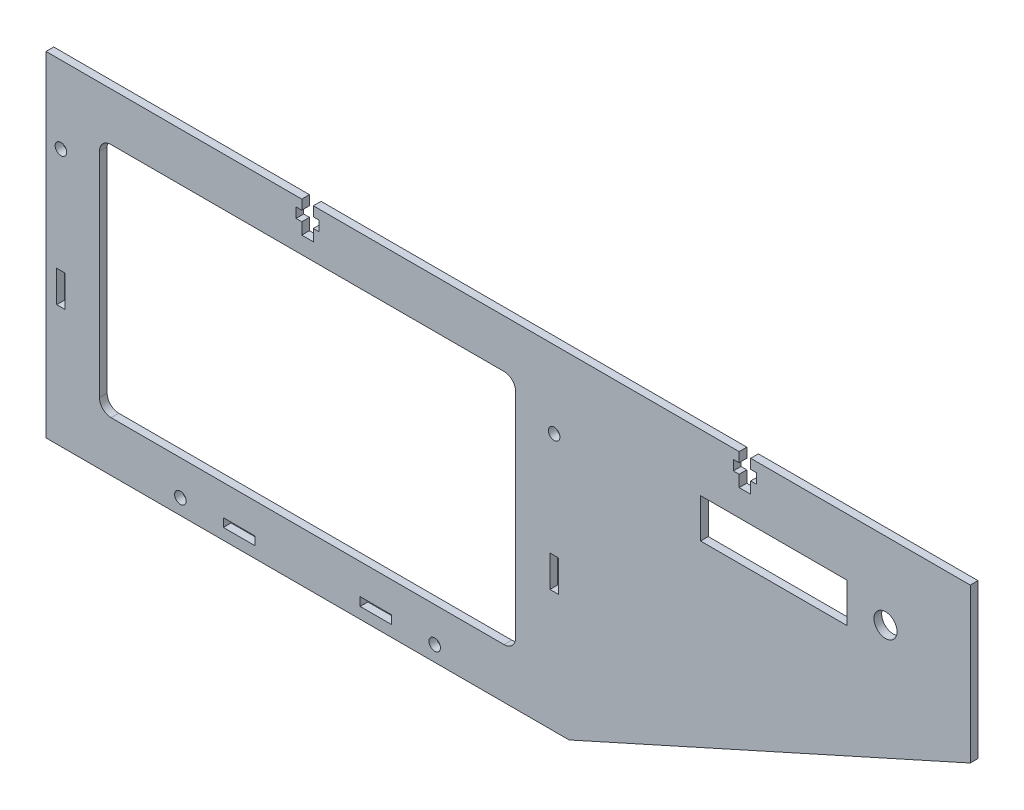
SolidWorks part; units mm, degrees
ref_plane "前视基准面" through (0, 0, 0) normal (0, 0, 1) x (1, 0, 0)
ref_plane "上视基准面" through (0, 0, 0) normal (0, 1, 0) x (1, 0, 0)
ref_plane "右视基准面" through (0, 0, 0) normal (1, 0, 0) x (0, 0, -1)
sketch "草图1" plane through (0, 0, 0) normal (0, 0, 1) x (1, 0, 0)
  line L0 (21.5651, -10.096) -> (13.5651, -8.096) construction
  line L1 (32.8151, -9.096) -> (-33.1849, -9.096) construction
  line L3 (-34.6849, -10.096) -> (-31.6849, -8.096) construction
  line L4 (-21.9349, -10.096) -> (-13.9349, -8.096) construction
  line L5 (-22.0349, -10.196) -> (-13.8349, -10.196)
  line L6 (-13.8349, -7.996) -> (-13.8349, -10.196)
  line L7 (-22.0349, -7.996) -> (-13.8349, -7.996)
  line L8 (-22.0349, -7.996) -> (-22.0349, -10.196)
  line L12 (-52.1849, -13.096) -> (-18.9349, -13.096)
  line L13 (64.9151, 18.2415) -> (62.7151, 18.2415)
  line L15 (34.3151, -10.096) -> (31.3151, -8.096) construction
  line L16 (21.6651, -7.996) -> (21.6651, -10.196)
  line L17 (21.6651, -7.996) -> (13.4651, -7.996)
  line L18 (13.4651, -7.996) -> (13.4651, -10.196)
  line L19 (67.6951, -13.096) -> (18.5651, -13.096)
  line L20 (64.9151, 18.2415) -> (64.9151, 26.4415)
  line L21 (-18.9349, -13.096) -> (18.5651, -13.096)
  line L22 (64.9151, 26.4415) -> (62.7151, 26.4415)
  line L25 (-63.0849, 18.2415) -> (-63.0849, 26.4415)
  line L26 (-65.2849, 26.4415) -> (-63.0849, 26.4415)
  line L27 (-65.2849, 18.2415) -> (-65.2849, 26.4415)
  line L28 (-65.2849, 18.2415) -> (-63.0849, 18.2415)
  line L29 (21.6651, -10.196) -> (13.4651, -10.196)
  line L34 (62.7151, 18.2415) -> (62.7151, 26.4415)
  line L35 (-52.1849, -13.096) -> (-68.0618, -13.096)
  line L41 (-49.1849, 53.779) -> (-49.1849, 33.779) construction
  line L42 (-49.1849, 53.779) -> (-49.1849, 73.779) construction
  line L43 (-68.0618, -13.096) -> (-68.0618, 73.779)
  line L46 (-49.1849, 53.779) -> (237.809, 53.779) construction
  line L47 (54.8151, 73.779) -> (54.8151, 87.1175) construction
  line L48 (54.8151, 87.1175) -> (171.8151, 87.1175) construction
  line L49 (-49.1849, 33.779) -> (206.8345, 33.779) construction
  line L50 (113.3151, 87.1175) -> (113.3151, 11.0003) construction
  line L51 (54.8151, 87.1175) -> (-62.1849, 87.1175) construction
  line L52 (-0.1849, -9.096) -> (-0.1849, 138.1567) construction
  line L53 (-1.6849, 71.279) -> (-3.1849, 71.279)
  line L59 (67.6951, -13.096) -> (171.8151, 33.779)
  line L60 (171.8151, 73.779) -> (171.8151, 33.779)
  line L61 (1.3151, 71.279) -> (2.8151, 71.279)
  line L62 (1.3151, 73.779) -> (1.3151, 71.279)
  line L63 (-3.1849, 71.279) -> (-3.1849, 68.679)
  line L64 (-3.1849, 68.679) -> (-1.6849, 68.679)
  line L65 (-1.6849, 68.679) -> (-1.6849, 65.679)
  line L66 (1.3151, 65.679) -> (-1.6849, 65.679)
  line L67 (1.3151, 68.679) -> (1.3151, 65.679)
  line L68 (2.8151, 68.679) -> (1.3151, 68.679)
  line L69 (2.8151, 71.279) -> (2.8151, 68.679)
  line L70 (-1.6849, 71.279) -> (-1.6849, 73.779)
  line L71 (-68.0618, 73.779) -> (-1.6849, 73.779)
  line L73 (-0.1849, 73.779) -> (-0.1849, 71.279) construction
  line L74 (139.8151, 53.779) -> (149.8151, 53.779) construction
  line L76 (114.8151, 73.779) -> (171.8151, 73.779)
  line L77 (111.8151, 71.279) -> (110.3151, 71.279)
  line L78 (114.8151, 71.279) -> (116.3151, 71.279)
  line L79 (114.8151, 73.779) -> (114.8151, 71.279)
  line L80 (110.3151, 71.279) -> (110.3151, 68.679)
  line L81 (110.3151, 68.679) -> (111.8151, 68.679)
  line L82 (111.8151, 68.679) -> (111.8151, 65.679)
  line L83 (114.8151, 65.679) -> (111.8151, 65.679)
  line L84 (114.8151, 68.679) -> (114.8151, 65.679)
  line L85 (116.3151, 68.679) -> (114.8151, 68.679)
  line L86 (116.3151, 71.279) -> (116.3151, 68.679)
  line L87 (111.8151, 71.279) -> (111.8151, 73.779)
  line L88 (114.8151, 65.679) -> (124.8151, 65.679) construction
  line L89 (113.3151, 73.779) -> (113.3151, 71.279) construction
  line L91 (1.3151, 73.779) -> (111.8151, 73.779)
  line L92 (124.8151, 53.779) -> (124.8151, 48.679) construction
  line L97 (124.8151, 48.679) -> (139.8151, 48.679)
  line L98 (139.8151, 48.679) -> (139.8151, 58.879)
  line L99 (139.8151, 58.879) -> (124.8151, 58.879)
  line L100 (111.8151, 65.679) -> (101.8151, 65.679) construction
  line L101 (101.8151, 58.879) -> (101.8151, 48.679)
  line L102 (101.8151, 48.679) -> (124.8151, 48.679)
  line L103 (124.8151, 58.879) -> (101.8151, 58.879)
  line L104 (-0.1849, 22.3415) -> (67.6951, 22.3415) construction
  line L105 (53.8151, 58.279) -> (53.8151, 2.904)
  line L106 (63.8151, 71.279) -> (-64.1849, 71.279) construction
  line L107 (63.8151, 71.279) -> (63.8151, -10.096) construction
  line L108 (63.8151, -10.096) -> (-64.1849, -10.096) construction
  line L109 (-64.1849, 71.279) -> (-64.1849, -10.096) construction
  line L110 (50.8151, -0.096) -> (-51.1849, -0.096)
  line L111 (-54.1849, 58.279) -> (-54.1849, 2.904)
  line L112 (50.8151, 61.279) -> (-51.1849, 61.279)
  line L113 (53.8151, -0.096) -> (-54.1849, -0.096) construction
  line L114 (53.8151, 61.279) -> (53.8151, -0.096) construction
  line L115 (-54.1849, 61.279) -> (-54.1849, -0.096) construction
  line L116 (53.8151, 61.279) -> (-54.1849, 61.279) construction
  circle A0 centre (-33.1849, -9.096) radius 1.5
  circle A2 centre (32.8151, -9.096) radius 1.5
  circle A11 centre (149.8151, 53.779) radius 3
  arc A12 (50.8151, -0.096) -> (53.8151, 2.904) centre (50.8151, 2.904) ccw
  arc A13 (-51.1849, -0.096) -> (-54.1849, 2.904) centre (-51.1849, 2.904) cw
  arc A14 (-54.1849, 58.279) -> (-51.1849, 61.279) centre (-51.1849, 58.279) cw
  arc A15 (50.8151, 61.279) -> (53.8151, 58.279) centre (50.8151, 58.279) cw
  circle A16 centre (-64.1849, 53.779) radius 1.5
  circle A17 centre (63.8151, 53.779) radius 1.5
  point P66 (-19.749, 73.5671)
  dimension "D1" = 10
  dimension "D2" = 3
  dimension "D3" = 3
extrude "凸台-拉伸1" add sketch "草图1" along normal blind 2
sketch "草图3" plane through (0, 73.779, 0) normal (0, 1, 0) x (1, 0, 0)
  line L0 (-1.6849, -1) -> (1.3151, -1)
  line L1 (-1.6849, -2) -> (-1.6849, 0) construction
  line L2 (1.3151, -2) -> (1.3151, 0) construction
  line L3 (111.8151, -1) -> (114.8151, -1)
  line L4 (111.8151, -2) -> (111.8151, 0) construction
  line L5 (114.8151, -2) -> (114.8151, 0) construction
  circle A0 centre (-0.1849, -1) radius 1.5
  circle A1 centre (113.3151, -1) radius 1.5
